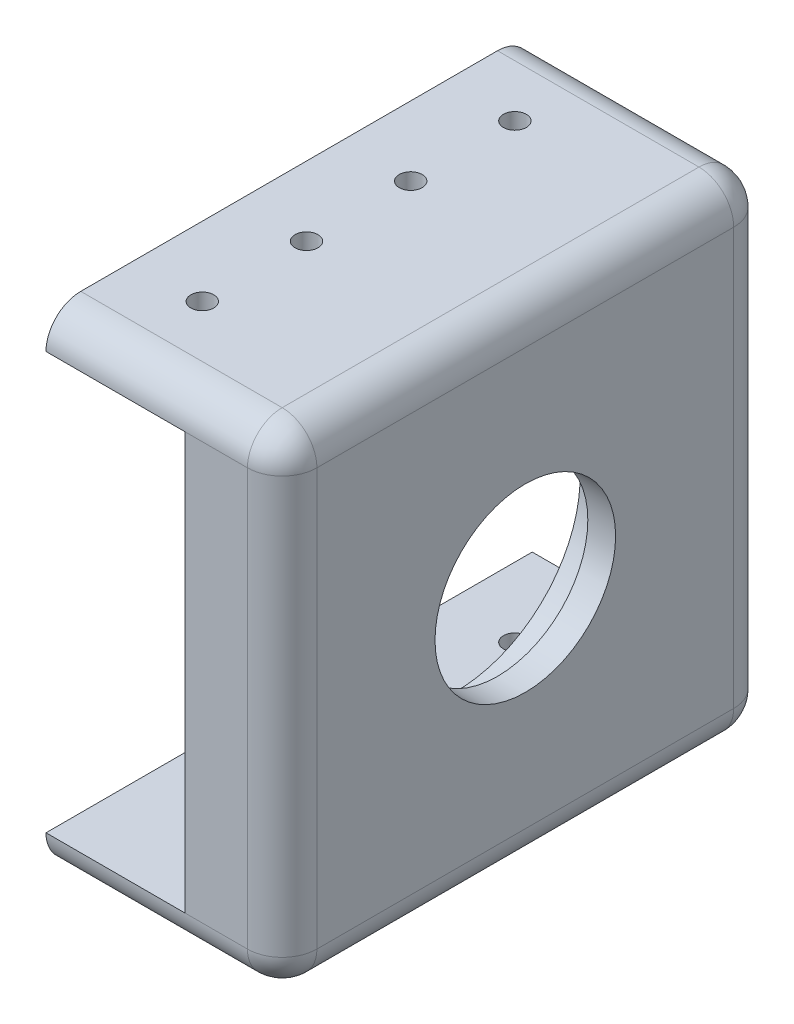
SolidWorks part; units mm, degrees
material "6061 Alloy"
ref_plane "Front Plane" through (0, 0, 0) normal (0, 0, 1) x (1, 0, 0)
ref_plane "Top Plane" through (0, 0, 0) normal (0, 1, 0) x (1, 0, 0)
ref_plane "Right Plane" through (0, 0, 0) normal (1, 0, 0) x (0, 0, -1)
sketch "Sketch1" plane through (0, 0, 0) normal (0, 0, 1) x (1, 0, 0)
  line L0 (0, -35) -> (0, 35)
  line L1 (-34, -35) -> (34, -35)
  line L2 (-34, -35) -> (-34, 35)
  line L3 (-34, 35) -> (34, 35)
  line L4 (34, -35) -> (34, 35)
  line L5 (-34, -35) -> (34, 35) construction
  line L6 (-34, 35) -> (34, -35) construction
  line L7 (-20, -30) -> (20, -30)
  line L8 (-20, -30) -> (-20, 30)
  line L9 (-20, 30) -> (20, 30)
  line L10 (20, -30) -> (20, 30)
  line L11 (-20, -30) -> (20, 30) construction
  line L12 (-20, 30) -> (20, -30) construction
  point P0 (0, 0)
  point P6 (0, 0)
  dimension "D1" = 60
  dimension "D2" = 70
  dimension "D3" = 40
  dimension "D4" = 68
extrude "Boss-Extrude1" add sketch "Sketch1" along normal blind 70 contours L10 L7 L0 L1 L4 L3 L9 region at (24.1186, 0, 0)
fillet "Fillet1" radius 5 4 edges at (17, -35, 70) (17, -35, 0) (17, 35, 0) (17, 35, 70)
fillet "Fillet2" radius 5 8 edges at (34, -33.5355, 1.4645) (34, -33.5355, 68.5355) (34, -35, 35) (34, 33.5355, 68.5355) (34, 0, 70) (34, 33.5355, 1.4645) (34, 0, 0) (34, 35, 35)
hole_wizard "M4x0.7 Tapped Hole1" positions "Sketch11" profile "Sketch12" tap size "M4x0.7" standard "ANSI Metric" end condition up to next
sketch "Sketch11" plane through (0, 35, 0) normal (0, 1, 0) x (1, 0, 0)
  line L0 (0, -65) -> (0, -5) construction
  line L1 (0, 0) -> (20, 0) construction
  point P0 (10, -12.5)
  point P2 (10, -27.5)
  point P4 (10, -42.5)
  point P6 (10, -57.5)
  dimension "D1" = 10
  dimension "D2" = 15
  dimension "D3" = 15
  dimension "D4" = 15
  dimension "D5" = 12.5
sketch "Sketch12" plane through (10, 35, 12.5) normal (1, 0, 0) x (0, 0, 1)
  line L0 (0, 0) -> (0, 5)
  line L1 (0, 5) -> (1.65, 5)
  line L2 (1.65, 5) -> (1.65, 0)
  line L5 (1.65, 0) -> (0, 0)
  line L11 (0, -6.35) -> (0, 107.95) construction
  dimension "Thread Major Dia." = 3.3
  dimension "Thru Tap Drill Depth" = 5
mirror "Mirror1" about plane through (0, 0, 0) normal (0, 1, 0) of "M4x0.7 Tapped Hole1"
sketch "Sketch13" plane through (20, 0, 0) normal (-1, 0, 0) x (0, 0, 1)
  line L0 (18.7, 0) -> (-18.7, 0) construction
  line L1 (70, 30) -> (0, 30) construction
  circle A0 centre (35, 0) radius 25
  point P6 (35, 30)
  dimension "D1" = 50
extrude "Cut-Extrude1" cut sketch "Sketch13" against normal blind 4
sketch "Sketch14" plane through (24, 0, 0) normal (-1, 0, 0) x (0, 0, 1)
  line L0 (18.7, 0) -> (-18.7, 0) construction
  circle A0 centre (35, 0) radius 17.9
  circle A1 centre (35, 0) radius 25 construction
  dimension "D1" = 35.8
extrude "Cut-Extrude2" cut sketch "Sketch14" against normal blind 2
sketch "Sketch15" plane through (26, 0, 0) normal (-1, 0, 0) x (0, 0, 1)
  circle A0 centre (35, 0) radius 17.5
  dimension "D1" = 35
extrude "Cut-Extrude3" cut sketch "Sketch15" against normal blind 4
sketch "Sketch16" plane through (30, 0, 0) normal (-1, 0, 0) x (0, 0, 1)
  circle A0 centre (35, 0) radius 13
  dimension "D1" = 26
extrude "Cut-Extrude4" cut sketch "Sketch16" against normal through all
sketch "Sketch17" plane through (26, 0, 0) normal (-1, 0, 0) x (0, 0, 1)
  line L0 (18.7, 0) -> (-18.7, 0) construction
  circle A0 centre (35, 0) radius 17.9
  circle A1 centre (35, 0) radius 13 construction
  circle A3 centre (35, 0) radius 17.9 construction
extrude "Cut-Extrude5" cut sketch "Sketch17" against normal blind 3
